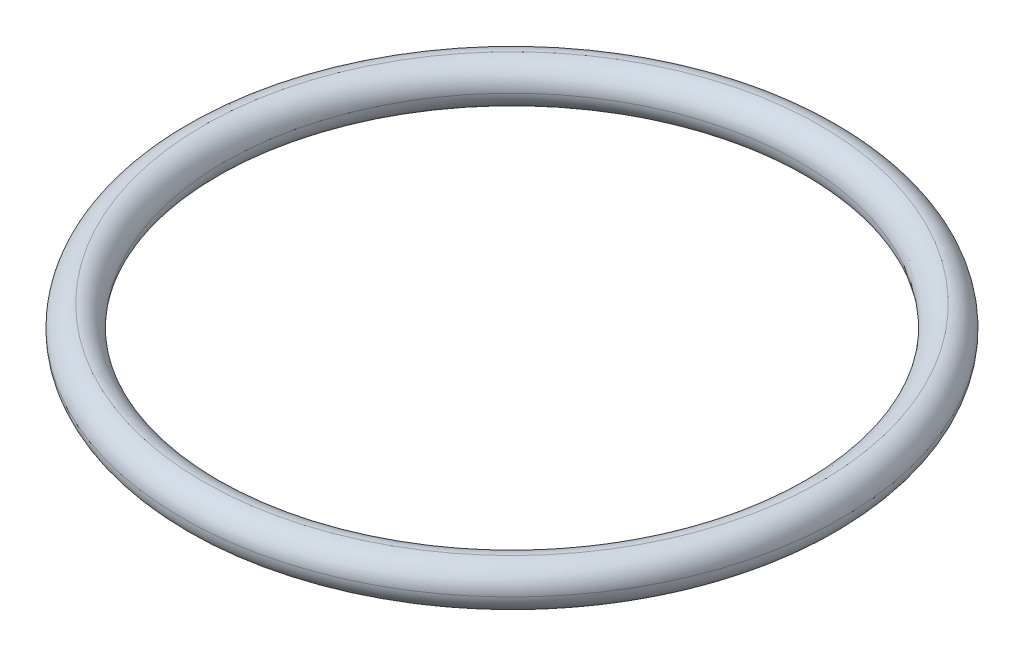
SolidWorks part; units mm, degrees
ref_plane "前视基准面" through (0, 0, 0) normal (0, 0, 1) x (1, 0, 0)
ref_plane "上视基准面" through (0, 0, 0) normal (0, 1, 0) x (1, 0, 0)
ref_plane "右视基准面" through (0, 0, 0) normal (1, 0, 0) x (0, 0, -1)
sketch "草图2" plane through (0, 0, 0) normal (0, 1, 0) x (1, 0, 0)
  circle A0 centre (0, 0) radius 23.5
  circle A1 centre (0, 0) radius 20.5
extrude "凸台-拉伸1" add sketch "草图2" along normal blind 3
fillet "圆角2" radius 1.5 4 edges at (0, 0, 20.5) (0, 0, 23.5) (0, 3, 20.5) (0, 3, 23.5)
